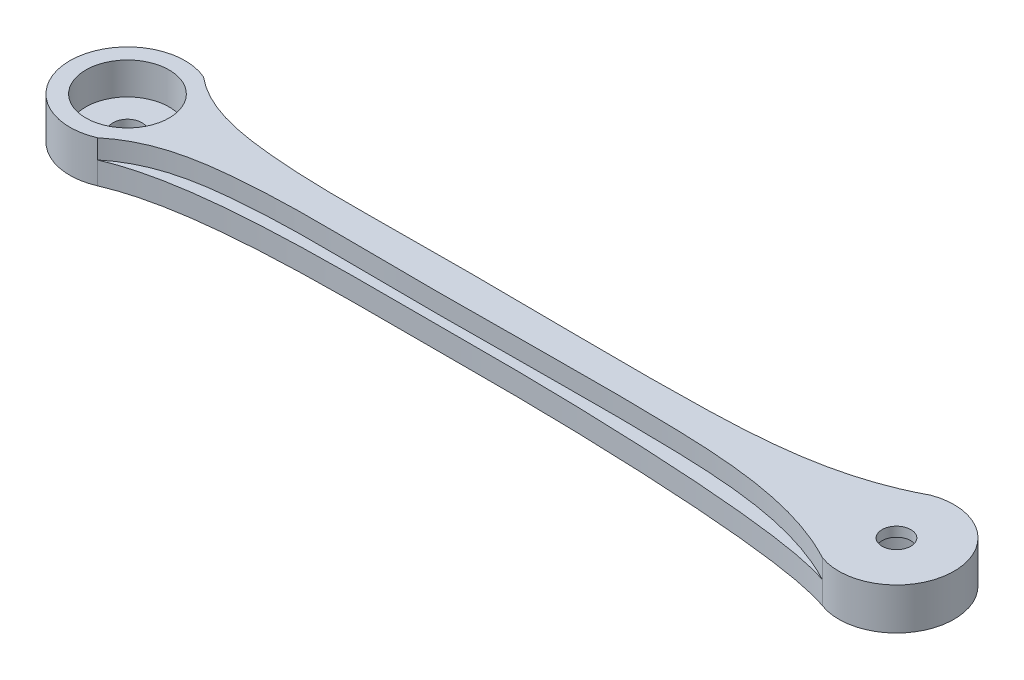
SolidWorks part; units mm, degrees
ref_plane "Front" through (0, 0, 0) normal (0, 0, 1) x (1, 0, 0)
ref_plane "Top" through (0, 0, 0) normal (0, 1, 0) x (1, 0, 0)
ref_plane "Right" through (0, 0, 0) normal (1, 0, 0) x (0, 0, -1)
sketch "Sketch1" plane through (0, 0, 0) normal (0, 1, 0) x (1, 0, 0)
  line L0 (-160.4656, 0) -> (44.4663, 0) construction
  line L1 (-106.6934, 4.0258) -> (-126.1258, 12.4799) construction
  line L2 (4.9211, 11.3545) -> (-11.0509, 5.5696) construction
  line L3 (-48.5627, 4) -> (-76.4251, 4) construction
  circle A0 centre (-120, 0) radius 2.25
  circle A1 centre (0, 0) radius 2.25
  circle A2 centre (-120, 0) radius 9
  circle A3 centre (0, 0) radius 9
  spline S0 degree 3 poles (-116.4096, 8.2528) (-105.4789, 3.4974) (-80.5324, 4.1285) (-45.7009, 3.8926) (-12.0492, 5.208) (-3.0649, 8.4621) knots 0 0 0 0 0.514413 0.614413 1 1 1 1
  spline S1 degree 3 poles (-116.4096, -8.2528) (-105.4789, -3.4974) (-80.5324, -4.1285) (-45.7009, -3.8926) (-12.0492, -5.208) (-3.0649, -8.4621) knots 0 0 0 0 0.514413 0.614413 1 1 1 1
  point P20 (-120, 9)
  dimension "D1" = 4.5
  dimension "D2" = 4.5
  dimension "D4" = 18
  dimension "D5" = 18
  dimension "D6" = 60
  dimension "D3" = 120
  dimension "D7" = 4
extrude "Boss-Extrude1" add sketch "Sketch1" along normal blind 6.5 contours A2 A0 | A2 S1 A3 S0 | A3 A1 region at (-112.6858, 0, 4.7943) region at (-58.2246, 0, 0) region at (5.0218, 0, -7.1599)
sketch "Sketch2" plane through (0, 6.5, 0) normal (0, 1, 0) x (1, 0, 0)
  circle A0 centre (-120, 0) radius 6.5
  circle A1 centre (0, 0) radius 6.5
  circle M1 centre (-120, 0) radius 2.25
  dimension "D1" = 13
  dimension "D2" = 13
extrude "Cut-Extrude1" cut sketch "Sketch2" against normal blind 5 contours A0 M1 region at (-126.3162, 6.5, 0)
sketch "Sketch3" plane through (0, 6.5, 0) normal (0, 1, 0) x (1, 0, 0)
  line L0 (-137.6146, 0) -> (18.7805, 0) construction
  spline S0 degree 3 poles (1619.3029, 998.9257) (-352.9389, -13.1279) (-163.7052, 4.6916) (3.3612, 3.5604) (324.0175, 24.8705) (-1993.8382, 196.3398) knots -2.387867 -2.387867 -2.387867 -2.387867 0.514413 0.614413 2.408556 2.408556 2.408556 2.408556 only from (-116.4096, 8.2528) to (-3.0649, 8.4621) construction
  spline S1 degree 3 poles (1619.3029, -998.9257) (-352.9389, 13.1279) (-163.7052, -4.6916) (3.3612, -3.5604) (324.0175, -24.8705) (-1993.8382, -196.3398) knots -2.387867 -2.387867 -2.387867 -2.387867 0.514413 0.614413 2.408556 2.408556 2.408556 2.408556 only from (-116.4096, -8.2528) to (-3.0649, -8.4621) construction
  spline S2 degree 3 poles (-116.4096, 8.2528) (-105.4789, 3.4974) (-80.5324, 4.1285) (-45.7009, 3.8926) (-12.0492, 5.208) (-3.0649, 8.4621) knots 0 0 0 0 0.514413 0.614413 1 1 1 1
  spline S3 degree 3 poles (-116.4096, -8.2528) (-105.4789, -3.4974) (-80.5324, -4.1285) (-45.7009, -3.8926) (-12.0492, -5.208) (-3.0649, -8.4621) knots 0 0 0 0 0.514413 0.614413 1 1 1 1
  spline S4 degree 3 poles (-116.4096, -8.2528) (-111.9265, -4.5151) (-103.6152, -3.0078) (-91.2207, -2.3473) (-77.849, -2.5685) (-58.0096, -2.5341) (-32.0985, -2.1177) (-12.4421, -3.4521) (-3.0649, -8.4621) knots 0 0 0 0 0.145433 0.214932 0.323765 0.493222 0.731337 1 1 1 1
  spline S5 degree 3 poles (-116.4096, 8.2528) (-111.9265, 4.5151) (-103.6152, 3.0078) (-91.2207, 2.3473) (-77.849, 2.5685) (-58.0096, 2.5341) (-32.0985, 2.1177) (-12.4421, 3.4521) (-3.0649, 8.4621) knots 0 0 0 0 0.145433 0.214932 0.323765 0.493222 0.731337 1 1 1 1
  spline M5 degree 3 poles (-116.4096, -8.2528) (-105.4789, -3.4974) (-80.5324, -4.1285) (-45.7009, -3.8926) (-12.0492, -5.208) (-3.0649, -8.4621) knots 0 0 0 0 0.514413 0.614413 1 1 1 1
  spline M7 degree 3 poles (-3.0649, 8.4621) (-12.0492, 5.208) (-45.7009, 3.8926) (-80.5324, 4.1285) (-105.4789, 3.4974) (-116.4096, 8.2528) knots 0 0 0 0 0.385587 0.485587 1 1 1 1
  dimension "D1" = 2.5
  dimension "D2" = 2.5
  dimension "D3" = 2.5
  dimension "D4" = 2.5
extrude "Cut-Extrude2" cut sketch "Sketch3" against normal blind 3 contours S4 M5 | S5 M7 region at (-58.4187, 6.5, -3.8966) region at (-58.4187, 6.5, 3.8966)
extrude "Cut-Extrude3" cut sketch "Sketch2<3>" along normal blind 5 from surface contours A1 starting at face at (-120, 0, 2.25)
sketch "Sketch2<3>" plane through (0, 6.5, 0) normal (0, 1, 0) x (1, 0, 0) same geometry as "Sketch2"
